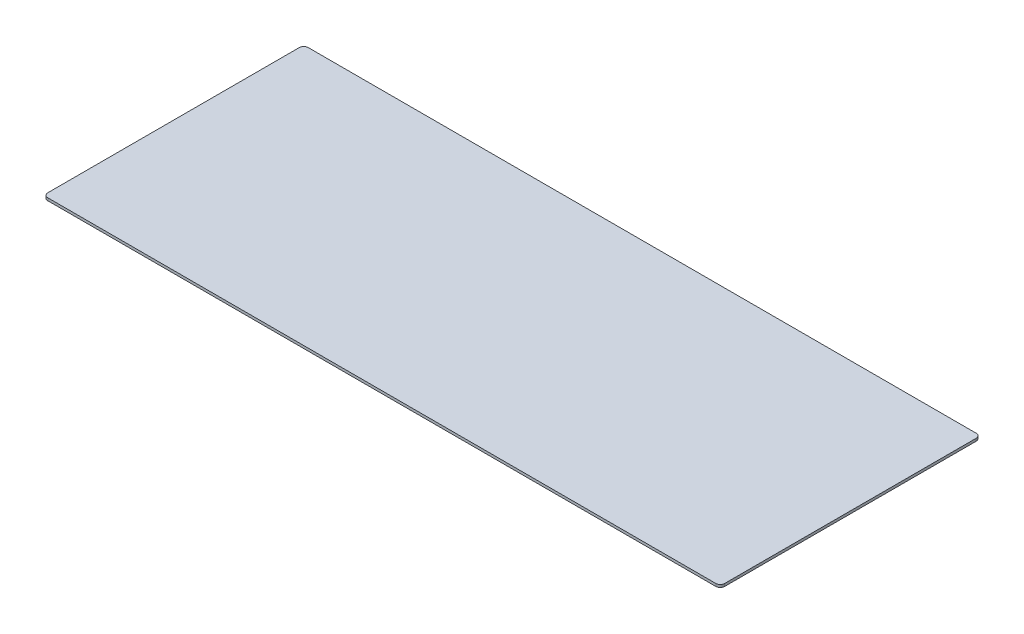
SolidWorks part; units mm, degrees
ref_plane "Front Plane" through (0, 0, 0) normal (0, 0, 1) x (1, 0, 0)
ref_plane "Top Plane" through (0, 0, 0) normal (0, 1, 0) x (1, 0, 0)
ref_plane "Right Plane" through (0, 0, 0) normal (1, 0, 0) x (0, 0, -1)
sketch "Sketch2" plane through (0, 0, 0) normal (0, 1, 0) x (1, 0, 0)
  line L1 (-390, 150) -> (390, 150)
  line L2 (-390, 150) -> (-390, -150)
  line L3 (-390, -150) -> (390, -150)
  line L4 (390, 150) -> (390, -150)
  dimension "D1" = 780
  dimension "D2" = 300
  dimension "D3" = 390
  dimension "D4" = 150
extrude "Boss-Extrude1" add sketch "Sketch2" along normal blind 3
fillet "Fillet1" radius 5 4 edges at (390, 1.5, -150) (390, 1.5, 150) (-390, 1.5, 150) (-390, 1.5, -150)
